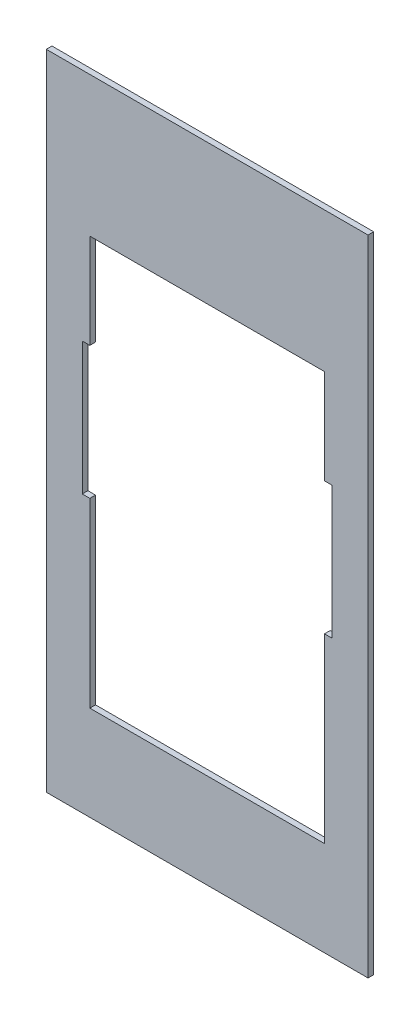
SolidWorks part; units mm, degrees
ref_plane "Front Plane" through (0, 0, 0) normal (0, 0, 1) x (1, 0, 0)
ref_plane "Top Plane" through (0, 0, 0) normal (0, 1, 0) x (1, 0, 0)
ref_plane "Right Plane" through (0, 0, 0) normal (1, 0, 0) x (0, 0, -1)
sketch "Sketch1" plane through (0, 0, 0) normal (0, 0, 1) x (1, 0, 0)
  line L1 (-42.5, 85) -> (42.5, 85)
  line L2 (-42.5, 85) -> (-42.5, -85)
  line L3 (-42.5, -85) -> (42.5, -85)
  line L4 (42.5, 85) -> (42.5, -85)
  line L5 (-42.5, 85) -> (42.5, -85) construction
  line L6 (-42.5, -85) -> (42.5, 85) construction
  line L20 (0, 0) -> (0, 96.4562) construction
  line L21 (0, 0) -> (0, -81.4119) construction
  line L22 (-31, -12) -> (-31, -60)
  line L23 (-31, 48) -> (31, 48)
  line L24 (-31, 48) -> (-31, 23)
  line L25 (-31, -60) -> (31, -60)
  line L26 (31, 48) -> (31, 23)
  line L27 (-31, 48) -> (31, -60) construction
  line L28 (-31, -60) -> (31, 48) construction
  line L29 (-31, 23) -> (-33, 23)
  line L31 (-31, -12) -> (-33, -12)
  line L32 (-33, 23) -> (-33, -12)
  line L33 (31, 23) -> (33, 23)
  line L35 (31, -12) -> (33, -12)
  line L36 (33, 23) -> (33, -12)
  line L37 (31, -12) -> (31, -60)
  point P0 (0, 0)
  point P6 (0, -6)
  dimension "D1" = 62
  dimension "D2" = 85
  dimension "D3" = 2
  dimension "D4" = 2
  dimension "D5" = 170
  dimension "D6" = 37
  dimension "D7" = 35
  dimension "D8" = 35
  dimension "D9" = 25
  dimension "D10" = 25
  dimension "D11" = 25
extrude "Boss-Extrude1" add sketch "Sketch1" along normal blind 1.5
